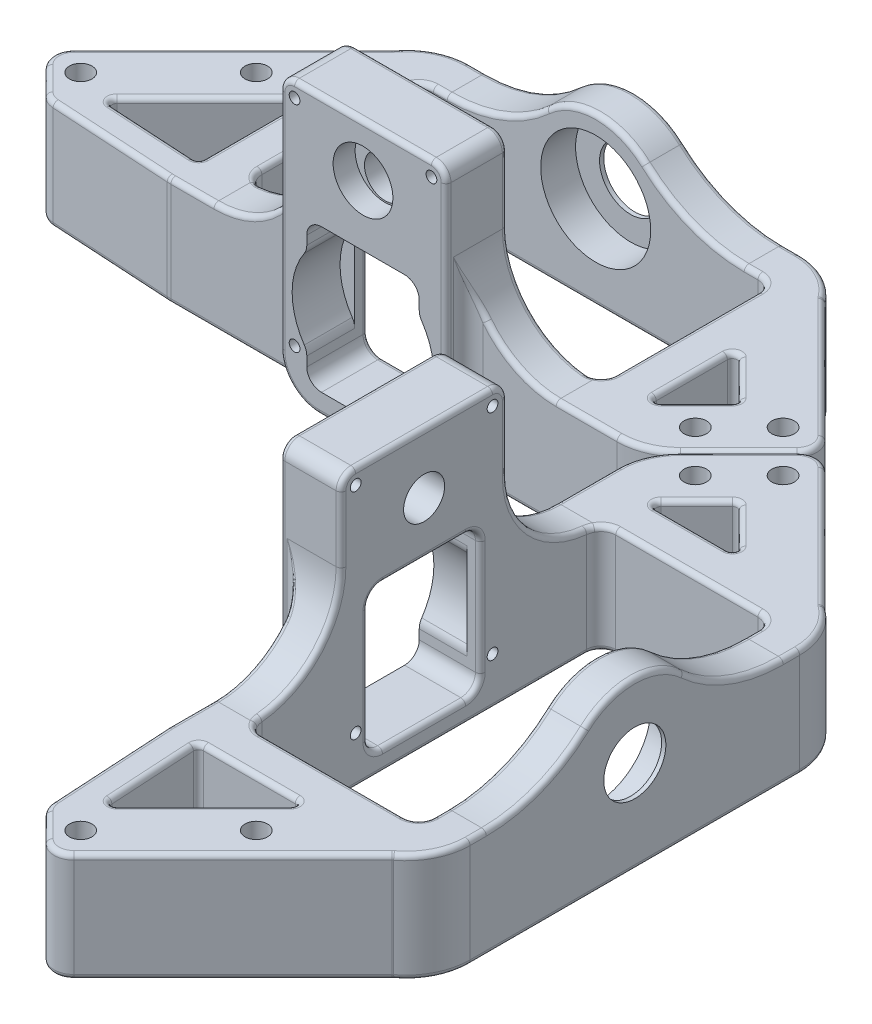
SolidWorks part; units mm, degrees
ref_plane "Front Plane" through (0, 0, 0) normal (0, 0, 1) x (1, 0, 0)
ref_plane "Top Plane" through (0, 0, 0) normal (0, 1, 0) x (1, 0, 0)
ref_plane "Right Plane" through (0, 0, 0) normal (1, 0, 0) x (0, 0, -1)
sketch "Sketch1" plane through (0, 0, 0) normal (0, 1, 0) x (1, 0, 0)
  line L0 (-44.195, -25.55) -> (-44.195, 25.55)
  line L1 (36.195, -17.55) -> (-36.195, -17.55)
  line L2 (36.195, -17.55) -> (36.195, 17.55)
  line L3 (36.195, 17.55) -> (-36.195, 17.55)
  line L4 (-36.195, -17.55) -> (-36.195, 17.55)
  line L5 (36.195, -17.55) -> (-36.195, 17.55) construction
  line L6 (36.195, 17.55) -> (-36.195, -17.55) construction
  line L11 (44.195, 25.55) -> (-44.195, 25.55)
  line L12 (44.195, -25.55) -> (44.195, 25.55)
  line L13 (44.195, -25.55) -> (-44.195, -25.55)
  line L14 (-79.6522, -15.223) -> (-70.8875, -23.9877)
  line L15 (-70.8875, -23.9877) -> (-44.195, 2.7047)
  line L16 (-79.6522, -15.223) -> (-44.195, 20.2342)
  line L17 (0, 0) -> (0, 65.6417) construction
  line L18 (-75.3776, -19.4976) -> (0, 55.88) construction
  line L19 (-44.195, -25.55) -> (-70.8875, -23.9877)
  line L20 (-44.195, -19.5397) -> (-65.2095, -18.3098)
  line L21 (0, 55.88) -> (62.8618, -6.9818) construction
  line L22 (62.8618, -6.9818) -> (53.8815, -15.962) construction
  line L23 (52.8428, -25.55) -> (71.411, -6.9818)
  line L24 (71.411, -6.9818) -> (44.195, 20.2342)
  line L25 (52.8428, -25.55) -> (44.195, -25.55)
  line L26 (-75.3776, -19.4976) -> (-269.4077, -213.5277) construction
  line L27 (44.195, 2.7047) -> (53.8815, -6.9818)
  line L28 (53.8815, -6.9818) -> (44.195, -16.6683)
  circle A0 centre (-71.842, -15.962) radius 2.3
  circle A1 centre (-53.8815, 1.9985) radius 2.3
  circle A6 centre (62.8618, -6.9818) radius 2.3
  circle A7 centre (53.8815, -15.962) radius 2.3
  point P0 (0, 0)
  point P21 (-75.3776, -19.4976)
  point P32 (-197.5656, -141.6856)
  point P34 (-215.5261, -159.6461)
  dimension "D10" = 4.6
  dimension "D24" = 4.6
  dimension "D1" = 8
  dimension "D2" = 45
  dimension "D3" = 55.88
  dimension "D4" = 5
  dimension "D5" = 76.2
  dimension "D6" = 12.3952
  dimension "D7" = 25.4
  dimension "D8" = 72.39
  dimension "D9" = 35.1
  dimension "D11" = 6
  dimension "D12" = 381
  dimension "D13" = 101.6
  dimension "D14" = 177.8
  dimension "D15" = 25.4
  dimension "D16" = 228.6
  dimension "D17" = 6.35
  dimension "D18" = 88.9
  dimension "D19" = 12.7
  dimension "D20" = 12.3952
  dimension "D21" = 6.35
  dimension "D22" = 12.3952
  dimension "D23" = 6.35
extrude "Boss-Extrude1" add sketch "Sketch1" along normal blind 22.25 contours L13 L12 L11 L0 L1 L4 L3 L2 | L27 L28 L12 L25 L23 L24 A7 A6 | L0 L20 L15 L19 | L16 L14 L15 L0 A1 A0 region at (-56.1781, 0, 21.9627) region at (-43.174, 0, 22.5449) region at (54.3256, 0, 5.3309) region at (-59.6388, 0, 3.5495)
extrude "Boss-Extrude2" add sketch "Sketch1<3>" along normal blind 15.85 from surface contours L13 L12 L11 L0 L1 L4 L3 L2 region at (-43.174, 0, 22.5449) starting at face at (-51.1998, 22.25, 11.7149)
sketch "Sketch1<3>" plane through (0, 0, 0) normal (0, 1, 0) x (1, 0, 0) same geometry as "Sketch1"
sketch "Sketch3" plane through (0, 0, 25.55) normal (0, 0, 1) x (1, 0, 0)
  line L0 (0, 0) -> (0, 38.1) construction
  line L1 (-44.195, 38.1) -> (44.195, 38.1) construction
  line L13 (-44.195, 22.25) -> (-17, 22.25)
  line L14 (-17, 22.25) -> (-17, 56.7)
  line L15 (-17, 56.7) -> (17, 56.7)
  line L16 (17, 56.7) -> (17, 22.25)
  line L17 (17, 22.25) -> (44.195, 22.25)
  line L18 (44.195, 38.1) -> (44.195, 22.25) construction
  line L19 (44.195, 22.25) -> (44.195, 38.1)
  line L20 (44.195, 38.1) -> (17, 38.1)
  line L21 (-17, 38.1) -> (-44.195, 38.1)
  line L22 (-44.195, 38.1) -> (-44.195, 22.25)
  line L23 (-17, 38.1) -> (17, 38.1)
  line L24 (11.5, 33.65) -> (-11.5, 33.65)
  line L25 (-11.5, 33.65) -> (-11.5, 27.8818)
  line L26 (11.5, 33.65) -> (11.5, 27.8818)
  line L27 (-44.195, 22.25) -> (-70.8875, 22.25) construction
  line L28 (52.8428, 0) -> (-44.195, 0) construction
  line L29 (11.5, 4.3) -> (-11.5, 4.3)
  line L30 (-11.5, 4.3) -> (-11.5, 10.2182)
  line L31 (11.5, 4.3) -> (11.5, 10.2182)
  line L32 (-11.5, 27.8818) -> (-11.5, 10.2182)
  line L33 (11.5, 27.8818) -> (11.5, 10.2182)
  circle A0 centre (14, 9.8) radius 1.1
  circle A1 centre (-14, 9.8) radius 1.1
  circle A2 centre (-14, 53.7) radius 1.1
  circle A3 centre (14, 53.7) radius 1.1
  circle A4 centre (0, 46.05) radius 6.114
  circle A20 centre (0, 44.45) radius 4.2
  circle A21 centre (0, 19.05) radius 14.5
  point P5 (0, 19.05)
  point P10 (0, 33.65)
  point P17 (0, 19.05)
  point P19 (0, 4.3)
  point P90 (-44.195, 22.25)
  line M46 (44.195, 22.25) -> (44.195, 38.1)
  line M47 (44.195, 38.1) -> (-44.195, 38.1)
  line M48 (-44.195, 38.1) -> (-44.195, 22.25)
  dimension "D1" = 2.2
  dimension "D5" = 12.228
  dimension "D6" = 8.4
  dimension "D8" = 1.6
  dimension "D14" = 34
  dimension "D15" = 29
  dimension "D2" = 3
  dimension "D3" = 3
  dimension "D4" = 3
  dimension "D7" = 25.4
  dimension "D9" = 28
  dimension "D10" = 43.9
  dimension "D11" = 34.45
  dimension "D12" = 27.195
  dimension "D13" = 19.05
  dimension "D16" = 23
  dimension "D17" = 14.6
  dimension "D18" = 14.75
extrude "Boss-Extrude3" add sketch "Sketch3" against normal up to surface (8 mm away) contours L16 L15 L14 L23 A4 A3 A2 M47 region at (-16.6124, 47.4, 25.55) up to face at (0, 19.05, 17.55)
extrude "Cut-Extrude1" cut sketch "Sketch3<3>" against normal up to next contours L13 L14 M47 M48 | L16 L17 M46 M47 region at (-30.5975, 30.175, 25.55) region at (30.5975, 30.175, 25.55)
sketch "Sketch3<3>" plane through (0, 0, 25.55) normal (0, 0, 1) x (1, 0, 0) same geometry as "Sketch3"
extrude "Cut-Extrude2" cut sketch "Sketch3<4>" against normal up to next contours L0 A21 | A21 L0 | L29 L0 A21 L30 | L0 L29 L31 A21 | L0 A21 L26 L24 | A21 L0 L24 L25 | A0 | A1 | L32 A21 | L33 A21 region at (-8.3672, 5.9503, 25.55) region at (8.3672, 5.9503, 25.55) region at (-5.3485, 19.05, 25.55) region at (5.3485, 19.05, 25.55) region at (-8.5839, 32.0193, 25.55) region at (8.5839, 32.0193, 25.55) region at (-12.7113, 19.05, 25.55) region at (12.7113, 19.05, 25.55) region at (14, 9.8, 25.55) region at (-14, 9.8, 25.55)
sketch "Sketch3<4>" plane through (0, 0, 25.55) normal (0, 0, 1) x (1, 0, 0) same geometry as "Sketch3"
sketch "Sketch4" plane through (0, 0, -25.55) normal (0, 0, -1) x (-1, 0, 0)
  line L0 (0, 0) -> (0, 38.1) construction
  line L1 (17, 38.1) -> (-17, 38.1) construction
  line L5 (-17, 22.25) -> (-14.6547, 22.25)
  line L6 (-17, 22.25) -> (-17, 38.1)
  line L7 (-17, 38.1) -> (17, 38.1)
  line L8 (17, 38.1) -> (17, 22.25)
  line L9 (17, 22.25) -> (14.6547, 22.25)
  circle A0 centre (0, 19.05) radius 6.35
  circle A1 centre (0, 19.05) radius 15
  line M7 (17, 22.25) -> (17, 38.1)
  line M8 (17, 38.1) -> (-17, 38.1)
  line M9 (-17, 38.1) -> (-17, 22.25)
  dimension "D1" = 30
  dimension "D2" = 12.7
extrude "Cut-Extrude3" cut sketch "Sketch4" against normal up to next contours A1 L0 L7 L5 M9 | L0 A1 L9 M7 M8 | L0 A0 | A0 L0 region at (2.695, 19.05, -25.55) region at (-2.695, 19.05, -25.55) region at (10.8276, 32.9317, -25.55) region at (-10.8276, 32.9317, -25.55)
extrude "Boss-Extrude6" add sketch "Sketch3<7>" along normal blind 2.7 from surface contours L32 A21 | L33 A21 region at (12.7113, 19.05, 25.55) region at (-12.7113, 19.05, 25.55) starting at face at (-12.9, 9.8, 17.55)
sketch "Sketch3<7>" plane through (0, 0, 25.55) normal (0, 0, 1) x (1, 0, 0) same geometry as "Sketch3"
sketch "Sketch9" plane through (0, 0, 25.55) normal (0, 0, 1) x (1, 0, 0)
  line L0 (-17, 22.25) -> (-17, 0)
  line L1 (17, 22.25) -> (17, 0)
  line L6 (-11.5, 33.65) -> (-11.5, 27.8818)
  line L7 (11.5, 33.65) -> (-11.5, 33.65)
  line L8 (11.5, 27.8818) -> (11.5, 33.65)
  line L9 (11.5, 4.3) -> (11.5, 10.2182)
  line L10 (-11.5, 4.3) -> (11.5, 4.3)
  line L11 (-11.5, 10.2182) -> (-11.5, 4.3)
  line L12 (-11.5, 33.65) -> (-11.5, 27.8818)
  line L13 (11.5, 33.65) -> (-11.5, 33.65)
  line L14 (11.5, 27.8818) -> (11.5, 33.65)
  line L15 (11.5, 4.3) -> (11.5, 10.2182)
  line L16 (-11.5, 4.3) -> (11.5, 4.3)
  line L17 (-11.5, 10.2182) -> (-11.5, 4.3)
  line L20 (-17, 22.25) -> (-44.195, 22.25)
  line L21 (-44.195, 22.25) -> (-44.195, 0)
  line L22 (-44.195, 0) -> (52.8428, 0)
  line L23 (52.8428, 0) -> (52.8428, 22.25)
  line L24 (52.8428, 22.25) -> (17, 22.25)
  line L25 (17, 22.25) -> (17, 56.7)
  line L26 (17, 56.7) -> (-17, 56.7)
  line L27 (-17, 56.7) -> (-17, 22.25)
  line L28 (-17, 22.25) -> (-44.195, 22.25)
  line L29 (-44.195, 22.25) -> (-44.195, 0)
  line L30 (-44.195, 0) -> (52.8428, 0)
  line L32 (52.8428, 22.25) -> (17, 22.25)
  line L33 (17, 22.25) -> (17, 56.7)
  line L34 (17, 56.7) -> (-17, 56.7)
  line L35 (-17, 56.7) -> (-17, 22.25)
  line L38 (52.8428, 0) -> (52.8428, 22.25)
  circle A1 centre (0, 46.05) radius 6.114
  circle A2 centre (0, 46.05) radius 6.114
  circle A3 centre (14, 53.7) radius 1.1
  circle A4 centre (14, 53.7) radius 1.1
  circle A5 centre (-14, 53.7) radius 1.1
  circle A6 centre (-14, 53.7) radius 1.1
  circle A7 centre (14, 9.8) radius 1.1
  circle A8 centre (14, 9.8) radius 1.1
  circle A9 centre (-14, 9.8) radius 1.1
  arc A10 (11.5, 10.2182) -> (11.5, 27.8818) centre (0, 19.05) ccw
  arc A11 (-11.5, 27.8818) -> (-11.5, 10.2182) centre (0, 19.05) ccw
  arc A12 (11.5, 10.2182) -> (11.5, 27.8818) centre (0, 19.05) ccw
  arc A13 (-11.5, 27.8818) -> (-11.5, 10.2182) centre (0, 19.05) ccw
  circle A14 centre (-14, 9.8) radius 1.1
  circle M22 centre (-14, 9.8) radius 1.1
  line M23 (-11.5, 27.8818) -> (-11.5, 33.65)
  line M24 (-11.5, 33.65) -> (11.5, 33.65)
  line M25 (11.5, 33.65) -> (11.5, 27.8818)
  arc M26 (11.5, 27.8818) -> (11.5, 10.2182) centre (0, 19.05) cw
  line M27 (11.5, 10.2182) -> (11.5, 4.3)
  line M28 (11.5, 4.3) -> (-11.5, 4.3)
  line M29 (-11.5, 4.3) -> (-11.5, 10.2182)
  arc M30 (-11.5, 10.2182) -> (-11.5, 27.8818) centre (0, 19.05) cw
  circle M31 centre (14, 9.8) radius 1.1
  line M34 (-44.195, 0) -> (52.8428, 0)
  line M37 (17, 22.25) -> (17, 56.7)
  line M38 (17, 56.7) -> (-17, 56.7)
  line M39 (-17, 56.7) -> (-17, 22.25)
  circle M40 centre (0, 46.05) radius 6.114
  circle M41 centre (14, 53.7) radius 1.1
  circle M42 centre (-14, 53.7) radius 1.1
  dimension "D1" = 0
  dimension "D2" = 0
  dimension "D3" = 0
  dimension "D4" = 0
  dimension "D5" = 0
  dimension "D6" = 0
  dimension "D7" = 0
extrude "Boss-Extrude7" add sketch "Sketch9" along normal blind 4.5 contours L1 L0 M37 M38 M39 M34 M30 M23 M24 M25 M26 M27 M28 M29 M31 M40 M42 M41 M22 region at (-16.3389, 39.475, 25.55)
fillet "Fillet1" radius 18 2 edges at (17, 22.25, 21.55) (-17, 22.25, 21.55)
fillet "Fillet2" radius 3 2 edges at (-17, 56.7, 23.8) (17, 56.7, 23.8)
fillet "Fillet4" radius 1 6 edges at (-44.195, 11.125, -2.7047) (-44.195, 11.125, 19.5397) (-65.2095, 11.125, 18.3098) (53.8815, 11.125, 6.9818) (44.195, 11.125, 16.6683) (44.195, 11.125, -2.7047)
fillet "Fillet5" radius 3 4 edges at (-36.195, 11.125, -17.55) (36.195, 11.125, -17.55) (36.195, 11.125, 17.55) (-36.195, 11.125, 17.55)
fillet "Fillet6" radius 13 4 edges at (44.195, 11.125, -25.55) (-44.195, 11.125, -25.55) (-44.195, 11.125, 25.55) (52.8428, 11.125, 25.55)
fillet "Fillet7" radius 4 3 edges at (-70.8875, 11.125, 23.9877) (-79.6522, 11.125, 15.223) (71.411, 11.125, 6.9818)
fillet "Fillet12" radius 8 2 edges at (-17, 0, 27.8) (17, 0, 27.8)
sketch "Sketch5" plane through (0, 0, -17.55) normal (0, 0, 1) x (1, 0, 0)
  circle A0 centre (0, 19.05) radius 11.25
  dimension "D1" = 22.5
extrude "Cut-Extrude4" cut sketch "Sketch5" against normal blind 7.1374
fillet "Fillet16" radius 3 4 edges at (14.6569, 2.3431, 25.55) (-14.6569, 2.3431, 25.55) (17, 24.125, 25.55) (-17, 24.125, 25.55)
fillet "Fillet8" radius 30 2 edges at (14.6547, 22.25, -21.55) (-14.6547, 22.25, -21.55)
fillet "Fillet10" radius 2 2 edges at (-44.195, 11.125, -20.2342) (44.195, 11.125, -20.2342)
fillet "Fillet9" radius 1 92 edges at (-34.1764, 22.2689, 17.3849) (-19.5142, 24.2857, -17.55) (0, 34.05, -17.55) (19.5142, 24.2857, -17.55) (35.3163, 22.25, -16.6713) (36.195, 22.25, 0) (35.8797, 22.25, 15.8888) (34.1145, 22.2718, 17.4056) (21.6492, 28.1771, 17.55) (17, 46.975, 17.55) (16.1213, 55.8213, 17.55) (0, 56.7, 17.55) (-16.1213, 55.8213, 17.55) (-17, 46.975, 17.55) (-19.5142, 24.2857, -25.55) (0, 34.05, -25.55) (19.5142, 24.2857, -25.55) (-32.0431, 22.25, -25.55) (-26.4882, 24.3897, 25.55) (-44.195, 22.25, 9.0945) (-35.3163, 0, 16.6713) (0, 0, 17.55) (35.3163, 0, 16.6713) (36.195, 0, 0) (35.3163, 0, -16.6713) (0, 0, -17.55) (-35.3163, 0, -16.6713) (44.195, 0, 6.9818) (-44.195, 0, 9.0945) (-21.6492, 28.1771, 17.55) (-36.195, 0, 0) (0, 0, -25.55) (-39.4074, 22.25, 25.55) (-35.8797, 22.25, 15.8888) (-36.195, 22.25, 0) (-35.3163, 22.25, -16.6713) (-31.786, 22.25, -17.55) (-44.5089, 0, 19.207) (-54.1195, 0, 18.9589) (-63.8618, 0, 17.7972) (-54.7682, 0, 7.8684) (-44.8123, 0, -1.2144) (-44.8123, 22.25, -1.2144) (-54.7682, 22.25, 7.8684) (-63.8618, 22.25, 17.7972) (-54.1195, 22.25, 18.9589) (-44.5089, 22.25, 19.207) (39.5259, 0, -24.1761) (-39.5259, 0, -24.1761) (-60.5616, 0, -3.8676) (-77.9953, 0, 15.223) (-44.1948, 0, 25.5444) (-56.9715, 0, 24.8022) (-70.773, 0, 23.7326) (-60.5616, 22.25, -3.8676) (-77.9953, 22.25, 15.223) (-44.1948, 22.25, 25.5444) (-56.9715, 22.25, 24.8022) (-70.773, 22.25, 23.7326) (-74.3935, 0, 20.4816) (-74.3935, 22.25, 20.4816) (-44.2025, 0, -20.2339) (-44.2025, 22.25, -20.2339) (-39.5259, 22.25, -24.1761) (-30.1824, 0, 25.55) (16.1213, 55.8213, 30.05) (0, 56.7, 30.05) (-16.1213, 55.8213, 30.05) (-17, 30.85, 30.05) (-14.6569, 2.3431, 30.05) (0, 0, 30.05) (14.6569, 2.3431, 30.05) (17, 30.85, 30.05) (14.0902, 0, 25.9624) (-14.0902, 0, 25.9624) (-18.5515, 32.9393, 25.9229) (44.8123, 0, 15.178) (49.5383, 0, 11.3251) (53.4673, 0, 6.9818) (49.5383, 0, 2.6385) (44.8123, 0, -1.2144) (32.0039, 0, 25.55) (52.4329, 0, 24.5604) (62.6165, 0, 15.7763) (69.7541, 0, 6.9818) (56.441, 0, -7.9882) (44.2025, 0, -20.2339) (44.8123, 22.25, -1.2144) (44.8123, 22.25, 15.178) (49.5383, 22.25, 11.3251) (53.4673, 22.25, 6.9818) (49.5383, 22.25, 2.6385)
fillet "Fillet11" radius 3 8 edges at (-11.5, 4.3, 23.8) (11.5, 4.3, 23.8) (11.5, 33.65, 23.8) (-11.5, 33.65, 23.8) (11.5, 27.8818, 25.15) (11.5, 10.2182, 25.15) (-11.5, 27.8818, 25.15) (-11.5, 10.2182, 25.15)
fillet "Fillet14" radius 1 8 edges at (-10.6213, 5.1787, 17.55) (-11.5, 18.975, 17.55) (-10.6213, 32.7713, 17.55) (0, 33.65, 17.55) (10.6213, 32.7713, 17.55) (11.5, 18.975, 17.55) (10.6213, 5.1787, 17.55) (0, 4.3, 17.55)
extrude "Boss-Extrude8" add sketch "Sketch3<8>" against normal up to surface (8 mm away) contours A4 A20 region at (-5.9411, 46.05, 25.55) up to face at (0, 18.975, 17.55)
sketch "Sketch3<8>" plane through (0, 0, 25.55) normal (0, 0, 1) x (1, 0, 0) same geometry as "Sketch3"
ref_plane "Plane1" through (39.1964, 0, 39.1964) normal (0.7071, 0, 0.7071) x (0.7071, 0, -0.7071)
mirror "Mirror1" about plane through (39.1964, 0, 39.1964) normal (0.7071, 0, 0.7071) of bodies 121
